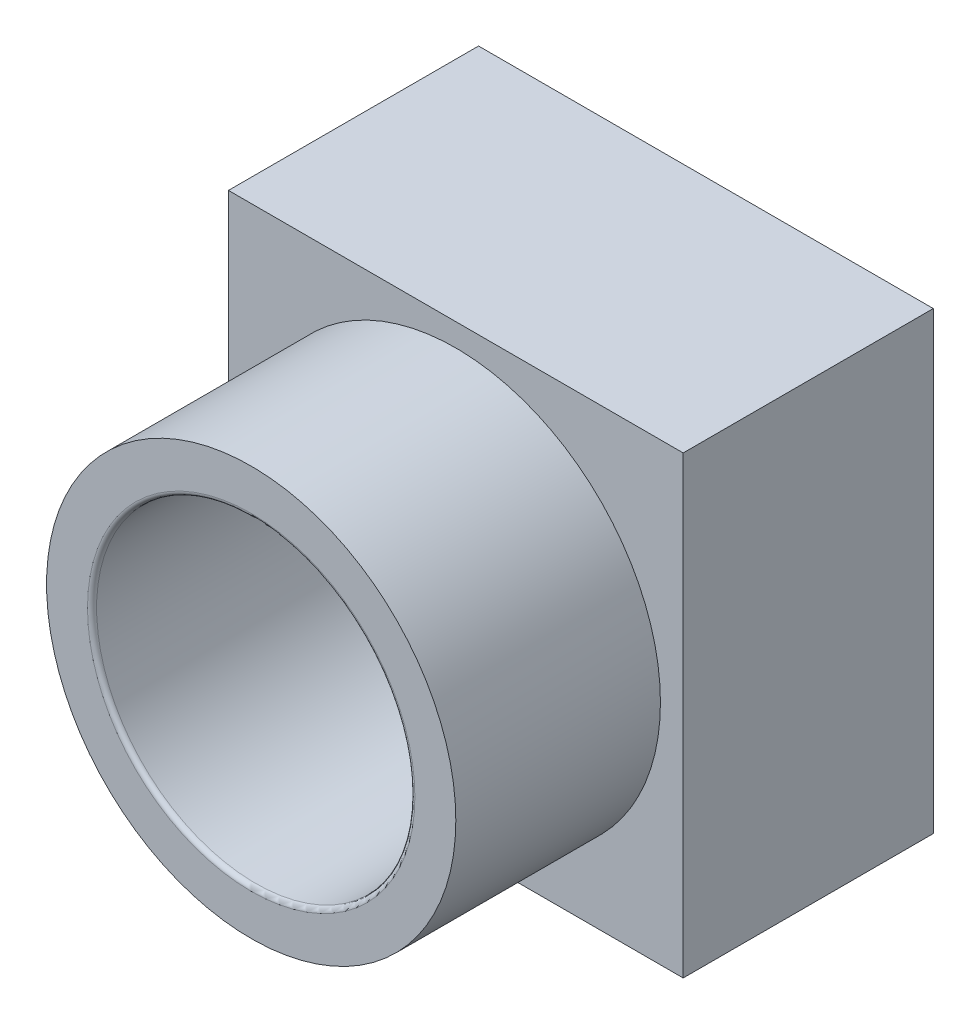
SolidWorks part; units mm, degrees
ref_plane "Front Plane" through (0, 0, 0) normal (0, 0, 1) x (1, 0, 0)
ref_plane "Top Plane" through (0, 0, 0) normal (0, 1, 0) x (1, 0, 0)
ref_plane "Right Plane" through (0, 0, 0) normal (1, 0, 0) x (0, 0, -1)
sketch "Sketch1" plane through (0, 0, 0) normal (0, 0, 1) x (1, 0, 0)
  line L1 (-12.7, 12.7) -> (12.7, 12.7)
  line L2 (-12.7, 12.7) -> (-12.7, -12.7)
  line L3 (-12.7, -12.7) -> (12.7, -12.7)
  line L4 (12.7, 12.7) -> (12.7, -12.7)
  line L5 (-12.7, 12.7) -> (12.7, -12.7) construction
  dimension "D1" = 25.4
  dimension "D2" = 25.4
extrude "Boss-Extrude1" add sketch "Sketch1" against normal blind 25.4
ref_plane "Plane1" through (0, 0, -13.97) normal (0, 0, 1) x (1, 0, 0)
sketch "Sketch2" plane through (0, 0, -13.97) normal (0, 0, 1) x (1, 0, 0)
  line L0 (-11.2268, 10.2235) -> (11.2268, -10.2235) construction
  line L1 (-11.2268, 10.2235) -> (11.2268, 10.2235)
  line L2 (-11.2268, 10.2235) -> (-11.2268, -10.2235)
  line L3 (-11.2268, -10.2235) -> (11.2268, -10.2235)
  line L4 (11.2268, 10.2235) -> (11.2268, -10.2235)
  point P4 (0, 0)
  dimension "D1" = 22.4536
  dimension "D2" = 20.447
extrude "Cut-Extrude1" cut sketch "Sketch2" against normal through all
sketch "Sketch3" plane through (0, 0, 0) normal (0, 0, 1) x (1, 0, 0)
  circle A0 centre (0, 0) radius 8.89
  dimension "D1" = 17.78
extrude "Cut-Extrude2" cut sketch "Sketch3" against normal through all both and the other way through all
ref_plane "Plane2" through (0, 0, -11.43) normal (0, 0, 1) x (1, 0, 0)
sketch "Sketch4" plane through (0, 0, -11.43) normal (0, 0, 1) x (1, 0, 0)
  circle A0 centre (0, 0) radius 8.89 construction
  circle A1 centre (0, 0) radius 8.89 construction
  circle A2 centre (0, 0) radius 11.43
  circle A3 centre (0, 0) radius 63.5
  dimension "D2" = 127
  dimension "D1" = 2.54
extrude "Cut-Extrude3" cut sketch "Sketch4" along normal through all
fillet "Fillet1" radius 1.27 4 edges at (0, -10.2235, -13.97) (11.2268, 0, -13.97) (0, 10.2235, -13.97) (-11.2268, 0, -13.97)
fillet "Fillet2" radius 1.27 8 edges at (-10.8548, -9.8515, -14.342) (-10.8548, 9.8515, -14.342) (10.8548, 9.8515, -14.342) (10.8548, -9.8515, -14.342) (-11.2268, -10.2235, -20.32) (-11.2268, 10.2235, -20.32) (11.2268, 10.2235, -20.32) (11.2268, -10.2235, -20.32)
fillet "Fillet3" radius 0.254 2 edges at (8.89, 0, -13.97) (8.89, 0, 0)
